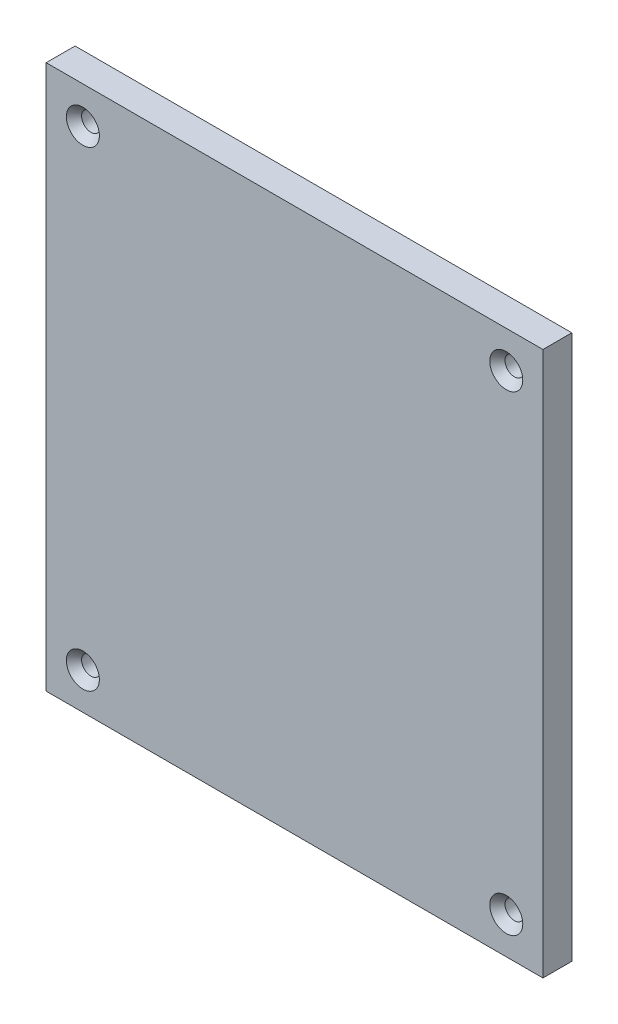
SolidWorks part; units mm, degrees
ref_plane "Front" through (0, 0, 0) normal (0, 0, 1) x (1, 0, 0)
ref_plane "Top" through (0, 0, 0) normal (0, 1, 0) x (1, 0, 0)
ref_plane "Right" through (0, 0, 0) normal (1, 0, 0) x (0, 0, -1)
sketch "Sketch1" plane through (0, 0, 0) normal (0, 0, 1) x (1, 0, 0)
  line L1 (-43, -47.117) -> (43, -47.117)
  line L2 (-43, -47.117) -> (-43, 47.117)
  line L3 (-43, 47.117) -> (43, 47.117)
  line L4 (43, -47.117) -> (43, 47.117)
  line L5 (-43, -47.117) -> (43, 47.117) construction
  line L6 (-43, 47.117) -> (43, -47.117) construction
  point P0 (0, 0)
  dimension "D1" = 86
  dimension "D2" = 94.234
extrude "Boss-Extrude1" add sketch "Sketch1" along normal blind 5
hole_wizard "CSK for #4 Flat Head Machine Screw1" positions "Sketch2" profile "Sketch3" countersink size "#4" standard "ANSI Inch" end condition up to next
sketch "Sketch2" plane through (0, 0, 5) normal (0, 0, 1) x (1, 0, 0)
  line L0 (43, 47.117) -> (-43, 47.117) construction
  line L1 (-43, 47.117) -> (-43, -47.117) construction
  line L2 (43, -47.117) -> (43, 47.117) construction
  line L3 (-43, -47.117) -> (43, -47.117) construction
  point P0 (-36.65, 40.767)
  point P2 (36.65, 40.767)
  point P4 (-36.65, -40.767)
  point P6 (36.65, -40.767)
  dimension "D1" = 6.35
  dimension "D2" = 6.35
  dimension "D3" = 6.35
  dimension "D4" = 6.35
sketch "Sketch3" plane through (-36.65, 40.767, 5) normal (1, 0, 0) x (0, -1, 0)
  line L0 (0, 0) -> (0, 5)
  line L1 (0, 5) -> (1.6319, 5)
  line L2 (1.6319, 5) -> (1.6319, 1.4098)
  line L3 (1.6319, 1.4098) -> (2.8575, 0)
  line L5 (2.8575, 0) -> (0, 0)
  line L6 (-1.6319, 1.4098) -> (-2.8575, 0) construction
  line L11 (0, -6.35) -> (0, 107.95) construction
  dimension "Thru Hole Dia." = 3.2639
  dimension "Thru Hole Depth" = 5
  dimension "Near C'Sink Dia." = 5.715
  dimension "Near C'Sink Angle" = 82
equation "\"PCB Width\"= 1940mil"
equation "\"PCB Height\"= 2210mil"
equation "\"PCB Thickness\"= 63mil"
equation "\"Motor Bearing Diameter\"= 12mm"
equation "\"Motor Bearing Length\"= 5mm"
equation "\"Motor Body Front Diameter\"= 37mm"
equation "\"Motor Body Front Length\"= 30mm"
equation "\"Motor Body Back Length\"= 33.3mm"
equation "\"Motor PCD\"= 31mm"
equation "\"Large PVC Fittings Wall Thickness\"= 15in / 64"
equation "\"Large PVC Pipe Outer Diameter\"= 3.5in"
equation "\"Box Width\"= 2 * \"Motor Bearing Length\" + \"Motor Body Front Length\" + \"Motor Body Back Length\" + 0.5in"
equation "\"Box Hole Center to Edge Distance\"= 250mil"
equation "\"Box Ceiling and Floor Thickness\"= 2 * \"Box Hole Center to Edge Distance\""
equation "\"Box Height\"= 2 * \"Box Ceiling and Floor Thickness\" + \"PCB Height\" + 0.5in"
equation "\"Box Back Depth\"= \"Large PVC Fittings Wall Thickness\" + \"Large PVC Pipe Outer Diameter\" / 2 + \"Motor Body Front Diameter\" / 2"
equation "\"D1@Sketch1\"=\"Box Width\""
equation "\"D2@Sketch1\"=\"Box Height\""
equation "\"D1@Boss-Extrude1\"=\"Motor Bearing Length\""
equation "\"D1@Sketch2\"=\"Box Hole Center to Edge Distance\""
equation "\"D2@Sketch2\"=\"Box Hole Center to Edge Distance\""
equation "\"D3@Sketch2\"=\"Box Hole Center to Edge Distance\""
equation "\"D4@Sketch2\"=\"Box Hole Center to Edge Distance\""
